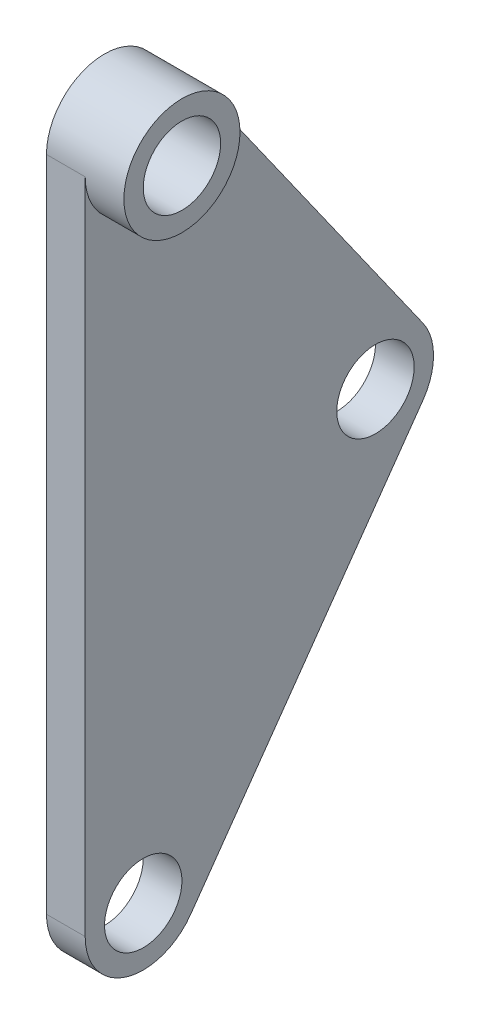
SolidWorks part; units mm, degrees
ref_plane "前视基准面" through (0, 0, 0) normal (0, 0, 1) x (1, 0, 0)
ref_plane "上视基准面" through (0, 0, 0) normal (0, 1, 0) x (1, 0, 0)
ref_plane "右视基准面" through (0, 0, 0) normal (1, 0, 0) x (0, 0, -1)
other "Configuration Table"
sketch "草图1" plane through (0, 0, 0) normal (1, 0, 0) x (0, 0, -1)
  line L0 (0, -20) -> (18, -20) construction
  line L1 (0, 0) -> (18, 0) construction
  line L2 (0, 0) -> (0, -40)
  line L3 (0, -40) -> (18, -40) construction
  line L4 (18, 0) -> (18, -40) construction
  line L5 (5.4509, -1.27) -> (17.4509, -18.27)
  line L6 (17.4509, -21.73) -> (5.4509, -38.73)
  circle A0 centre (3, -3) radius 3
  circle A1 centre (3, -37) radius 3
  circle A2 centre (15, -20) radius 3
  circle A3 centre (3, -3) radius 2
  circle A4 centre (15, -20) radius 2
  circle A5 centre (3, -37) radius 2
  dimension "D1" = 6
  dimension "D2" = 4
  dimension "D3" = 40
  dimension "D4" = 18
extrude "凸台-拉伸1" add sketch "草图1" along normal blind 2 contours A2 L5 A0 L2 A1 L6 | A0 | A2 | A1 region at (0, -20, -6.4523)
extrude "凸台-拉伸2" add sketch "草图1<4>" along normal blind 2 from surface contours A0 starting at face at (2, -20, -7.5145)
sketch "草图1<4>" plane through (0, 0, 0) normal (1, 0, 0) x (0, 0, -1) same geometry as "草图1"
extrude "切除-拉伸1" cut sketch "草图1<3>" along normal through all both and the other way through all contours A3 | A4 | A5
sketch "草图1<3>" plane through (0, 0, 0) normal (1, 0, 0) x (0, 0, -1) same geometry as "草图1"
